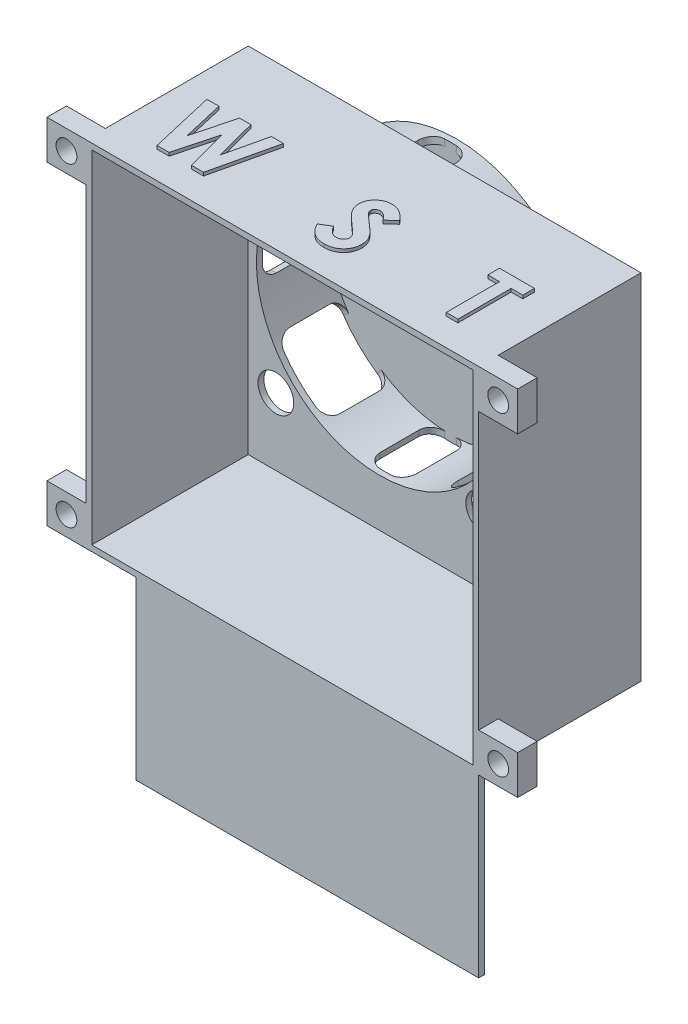
SolidWorks part; units mm, degrees
ref_plane "Alzado" through (0, 0, 0) normal (0, 0, 1) x (1, 0, 0)
ref_plane "Planta" through (0, 0, 0) normal (0, 1, 0) x (1, 0, 0)
ref_plane "Vista lateral" through (0, 0, 0) normal (1, 0, 0) x (0, 0, -1)
sketch "Croquis1" plane through (0, 0, 0) normal (0, 0, 1) x (1, 0, 0)
  line L1 (0, 0) -> (-60.5, 0)
  line L2 (0, 0) -> (0, 54.5)
  line L3 (0, 54.5) -> (-60.5, 54.5)
  line L4 (-60.5, 0) -> (-60.5, 54.5)
  dimension "D1" = 60.5
  dimension "D2" = 54.5
extrude "Saliente-Extruir1" add sketch "Croquis1" along normal blind 25
sketch "Croquis3" plane through (0, 0, 25) normal (0, 0, 1) x (1, 0, 0)
  line L8 (-0.9, 0.9) -> (-0.9, 53.6)
  line L9 (-0.9, 53.6) -> (-59.6, 53.6)
  line L10 (-59.6, 53.6) -> (-59.6, 0.9)
  line L11 (-59.6, 0.9) -> (-0.9, 0.9)
  line L12 (-0.9, 0.9) -> (-0.9, 53.6)
  line L13 (-0.9, 53.6) -> (-59.6, 53.6)
  line L14 (-59.6, 53.6) -> (-59.6, 0.9)
  line L15 (-59.6, 0.9) -> (-0.9, 0.9)
  dimension "D1" = 0.9
extrude "Cortar-Extruir1" cut sketch "Croquis3" against normal blind 24.1
sketch "Croquis9" plane through (0, 54.5, 0) normal (0, 1, 0) x (1, 0, 0)
  text T0 "W" font "Century Gothic" height 10
  text T1 "S" font "Century Gothic" height 10
  text T2 "T" font "Century Gothic" height 10
sketch "Croquis10" plane through (0, 0, 25) normal (0, 0, 1) x (1, 0, 0)
  line L0 (-30.25, 53.6) -> (-30.25, 0.9) construction
  line L1 (-60.5, 54.5) -> (-66.5, 54.5)
  line L2 (-60.5, 54.5) -> (-60.5, 48.5)
  line L3 (-60.5, 48.5) -> (-66.5, 48.5)
  line L4 (-66.5, 54.5) -> (-66.5, 48.5)
  line L5 (-0.9, 53.6) -> (-59.6, 53.6) construction
  line L6 (-59.6, 0.9) -> (-0.9, 0.9) construction
  line L7 (6, 54.5) -> (6, 48.5)
  line L8 (0, 48.5) -> (6, 48.5)
  line L9 (0, 54.5) -> (0, 48.5)
  line L10 (0, 54.5) -> (6, 54.5)
  line L11 (-59.6, 27.25) -> (-0.9, 27.25) construction
  line L12 (-59.6, 53.6) -> (-59.6, 0.9) construction
  line L13 (-0.9, 0.9) -> (-0.9, 53.6) construction
  line L14 (0, 0) -> (6, 0)
  line L15 (0, 0) -> (0, 6)
  line L16 (0, 6) -> (6, 6)
  line L17 (6, 0) -> (6, 6)
  line L18 (-66.5, 0) -> (-66.5, 6)
  line L19 (-60.5, 6) -> (-66.5, 6)
  line L20 (-60.5, 0) -> (-60.5, 6)
  line L21 (-60.5, 0) -> (-66.5, 0)
  circle A0 centre (-63.5, 51.5) radius 1.6
  circle A1 centre (3, 51.5) radius 1.6
  circle A2 centre (3, 3) radius 1.6
  circle A3 centre (-63.5, 3) radius 1.6
  dimension "D1" = 6
  dimension "D2" = 6
extrude "Saliente-Extruir3" add sketch "Croquis10" against normal blind 3
extrude "Saliente-Extruir5" add sketch "Croquis9" along normal blind 0.5
sketch "Croquis13" plane through (0, 0, 0) normal (0, -1, 0) x (1, 0, 0)
  line L0 (-66.5, 25) -> (6, 25) construction
  line L5 (0, 25) -> (-52.75, 25)
  line L6 (0, 25) -> (0, 24.1)
  line L7 (0, 24.1) -> (-52.75, 24.1)
  line L8 (-52.75, 25) -> (-52.75, 24.1)
  point P7 (0, 20.982)
  dimension "D1" = 52.75
  dimension "D2" = 0.9
extrude "Saliente-Extruir6" add sketch "Croquis13" along normal blind 27.07
sketch "Croquis14" plane through (0, 0, 0) normal (0, 0, -1) x (-1, 0, 0)
  line L0 (60.5, 54.5) -> (60.5, 0) construction
  line L1 (23.3412, 43.25) -> (55.3412, 43.25) construction
  line L2 (23.3412, 43.25) -> (23.3412, 11.25) construction
  line L3 (23.3412, 11.25) -> (55.3412, 11.25) construction
  line L4 (55.3412, 43.25) -> (55.3412, 11.25) construction
  line L5 (23.3412, 43.25) -> (55.3412, 11.25) construction
  line L6 (23.3412, 11.25) -> (55.3412, 43.25) construction
  line L7 (0, 0) -> (0, 54.5) construction
  line L8 (16.2, 3.75) -> (3, 3.75)
  line L9 (16.2, 3.75) -> (16.2, 23.25)
  line L10 (16.2, 23.25) -> (3, 23.25)
  line L11 (3, 3.75) -> (3, 23.25)
  line L12 (0, 27.25) -> (20.3412, 27.25) construction
  line L13 (16.2, 31.25) -> (3, 31.25)
  line L14 (3, 50.75) -> (3, 31.25)
  line L15 (16.2, 50.75) -> (3, 50.75)
  line L16 (16.2, 50.75) -> (16.2, 31.25)
  circle A0 centre (39.3412, 27.25) radius 19
  circle A1 centre (55.3412, 11.25) radius 2.75
  circle A2 centre (23.3412, 11.25) radius 2.75
  circle A3 centre (23.3412, 43.25) radius 2.75
  circle A4 centre (55.3412, 43.25) radius 2.75
  point P15 (39.3412, 27.25)
  point P19 (60.5, 27.25)
  dimension "D1" = 32
  dimension "D3" = 38
  dimension "D4" = 5.5
  dimension "D2" = 32
  dimension "D6" = 19.5
  dimension "D7" = 13.2
  dimension "D8" = 3
  dimension "D9" = 4
  dimension "D5" = 4
extrude "Cortar-Extruir2" cut sketch "Croquis14" against normal up to vertex (0.9 mm away) up to point (-0.9, 0.9, 0.9)
sketch "Croquis15" plane through (0, 0, 0) normal (0, 0, -1) x (-1, 0, 0)
  line L0 (39.3412, 27.25) -> (20.3412, 27.25) construction
  line L1 (39.3412, 27.25) -> (29.8412, 9.6503) construction
  line L2 (39.3412, 27.25) -> (23.3412, 11.25) construction
  line L3 (39.3412, 27.25) -> (21.7414, 17.75) construction
  line L4 (39.3412, 27.25) -> (21.7414, 36.75) construction
  line L5 (21.7414, 17.75) -> (22.6214, 18.225)
  line L6 (21.7414, 36.75) -> (22.6214, 36.275)
  line L13 (19.3412, 27.25) -> (19.3412, 24.25) construction
  line L14 (39.3412, 27.25) -> (19.3412, 24.25) construction
  line L15 (39.3412, 27.25) -> (19.3412, 30.25) construction
  line L16 (19.5624, 24.2832) -> (20.5514, 24.4315)
  line L17 (19.5624, 30.2168) -> (20.5514, 30.0685)
  line L18 (29.8412, 44.8497) -> (30.3162, 43.9697)
  line L19 (48.8412, 44.8497) -> (48.3662, 43.9697)
  line L20 (36.3743, 47.0287) -> (36.5227, 46.0398)
  line L21 (42.308, 47.0287) -> (42.1596, 46.0398)
  line L22 (56.9409, 36.75) -> (56.0609, 36.275)
  line L23 (56.9409, 17.75) -> (56.0609, 18.225)
  line L24 (59.1199, 30.2168) -> (58.1309, 30.0685)
  line L25 (59.1199, 24.2832) -> (58.1309, 24.4315)
  line L26 (48.8412, 9.6503) -> (48.3662, 10.5303)
  line L27 (29.8412, 9.6503) -> (30.3162, 10.5303)
  line L28 (42.308, 7.4713) -> (42.1596, 8.4602)
  line L29 (36.3743, 7.4713) -> (36.5227, 8.4602)
  arc A0 (22.6214, 36.275) -> (20.5514, 30.0685) centre (39.3412, 27.25) ccw
  arc A1 (21.7414, 36.75) -> (19.5624, 30.2168) centre (39.3412, 27.25) ccw
  arc A8 (20.5514, 24.4315) -> (22.6214, 18.225) centre (39.3412, 27.25) ccw
  arc A9 (19.5624, 24.2832) -> (21.7414, 17.75) centre (39.3412, 27.25) ccw
  arc A10 (48.3662, 43.9697) -> (42.1596, 46.0398) centre (39.3412, 27.25) ccw
  arc A11 (48.8412, 44.8497) -> (42.308, 47.0287) centre (39.3412, 27.25) ccw
  arc A12 (36.5227, 46.0398) -> (30.3162, 43.9697) centre (39.3412, 27.25) ccw
  arc A13 (36.3743, 47.0287) -> (29.8412, 44.8497) centre (39.3412, 27.25) ccw
  arc A14 (56.0609, 18.225) -> (58.1309, 24.4315) centre (39.3412, 27.25) ccw
  arc A15 (56.9409, 17.75) -> (59.1199, 24.2832) centre (39.3412, 27.25) ccw
  arc A16 (58.1309, 30.0685) -> (56.0609, 36.275) centre (39.3412, 27.25) ccw
  arc A17 (59.1199, 30.2168) -> (56.9409, 36.75) centre (39.3412, 27.25) ccw
  arc A18 (30.3162, 10.5303) -> (36.5227, 8.4602) centre (39.3412, 27.25) ccw
  arc A19 (29.8412, 9.6503) -> (36.3743, 7.4713) centre (39.3412, 27.25) ccw
  arc A20 (42.1596, 8.4602) -> (48.3662, 10.5303) centre (39.3412, 27.25) ccw
  arc A21 (42.308, 7.4713) -> (48.8412, 9.6503) centre (39.3412, 27.25) ccw
  point P24 (39.3412, 27.25)
  point P45 (39.3412, 27.25)
  dimension "D1" = 1
  dimension "D2" = 4
extrude "Saliente-Extruir7" add sketch "Croquis15" along normal blind 10
sketch "Croquis16" plane through (0, 0, -10) normal (0, 0, -1) x (-1, 0, 0)
  circle A1 centre (39.3412, 27.25) radius 20
extrude "Saliente-Extruir8" add sketch "Croquis16" along normal blind 0.9
fillet "Redondeo2" radius 2 32 edges at (-56.5009, 36.5125, -10) (-56.5009, 36.5125, 0) (-56.5009, 17.9875, -10) (-56.5009, 17.9875, 0) (-58.6254, 30.1426, 0) (-58.6254, 30.1426, -10) (-58.6254, 24.3574, -10) (-58.6254, 24.3574, 0) (-36.4485, 7.9657, 0) (-48.6037, 10.0903, 0) (-48.6037, 10.0903, -10) (-36.4485, 7.9657, -10) (-30.0787, 10.0903, -10) (-42.2338, 7.9657, -10) (-22.1814, 17.9875, -10) (-20.0569, 30.1426, -10) (-20.0569, 30.1426, 0) (-22.1814, 17.9875, 0) (-42.2338, 7.9657, 0) (-30.0787, 10.0903, 0) (-20.0569, 24.3574, 0) (-30.0787, 44.4097, 0) (-30.0787, 44.4097, -10) (-42.2338, 46.5343, -10) (-22.1814, 36.5125, -10) (-36.4485, 46.5343, -10) (-22.1814, 36.5125, 0) (-36.4485, 46.5343, 0) (-42.2338, 46.5343, 0) (-48.6037, 44.4097, 0) (-48.6037, 44.4097, -10) (-20.0569, 24.3574, -10)
sketch "Croquis17" plane through (0, 0, -10.9) normal (0, 0, -1) x (-1, 0, 0)
  line L0 (39.3412, 27.25) -> (19.3412, 27.25) construction
  line L1 (39.3412, 27.25) -> (39.3412, 22.25) construction
  line L2 (49.3412, 22.25) -> (29.3412, 22.25) construction
  line L3 (49.3412, 37.25) -> (29.3412, 37.25) construction
  line L4 (39.3412, 27.25) -> (22.0111, 37.2335) construction
  line L5 (22.0111, 37.2335) -> (22.9294, 33.8193)
  line L6 (22.9294, 33.8193) -> (23.6782, 35.1191)
  line L7 (23.6782, 35.1191) -> (26.2777, 33.6215)
  line L8 (26.2777, 33.6215) -> (27.2761, 35.3545)
  line L9 (22.0111, 37.2335) -> (25.4253, 38.1518)
  line L10 (25.4253, 38.1518) -> (24.6766, 36.8521)
  line L11 (24.6766, 36.8521) -> (27.2761, 35.3545)
  line L12 (22.0111, 17.2665) -> (22.9294, 20.6807)
  line L13 (22.9294, 20.6807) -> (23.6782, 19.3809)
  line L14 (23.6782, 19.3809) -> (26.2777, 20.8785)
  line L15 (26.2777, 20.8785) -> (27.2761, 19.1455)
  line L16 (24.6766, 17.6479) -> (27.2761, 19.1455)
  line L17 (25.4253, 16.3482) -> (24.6766, 17.6479)
  line L18 (22.0111, 17.2665) -> (25.4253, 16.3482)
  circle A0 centre (39.3412, 27.25) radius 20 construction
  text T0 "SOLDER" font "Century Gothic" height 6
  text T1 "SOUND" font "Century Gothic" height 6
  point P8 (39.3412, 22.25)
  point P12 (39.3412, 37.25)
  point P19 (0, 0)
  point P21 (26.7769, 34.488)
  point P22 (22.0206, 37.25)
  point P23 (22.0111, 37.25)
  dimension "D1" = 20
  dimension "D2" = 10
  dimension "D3" = 45
  dimension "D4" = 1.5
  dimension "D5" = 3
  dimension "D6" = 1
extrude "Saliente-Extruir9" add sketch "Croquis17" along normal blind 0.9
